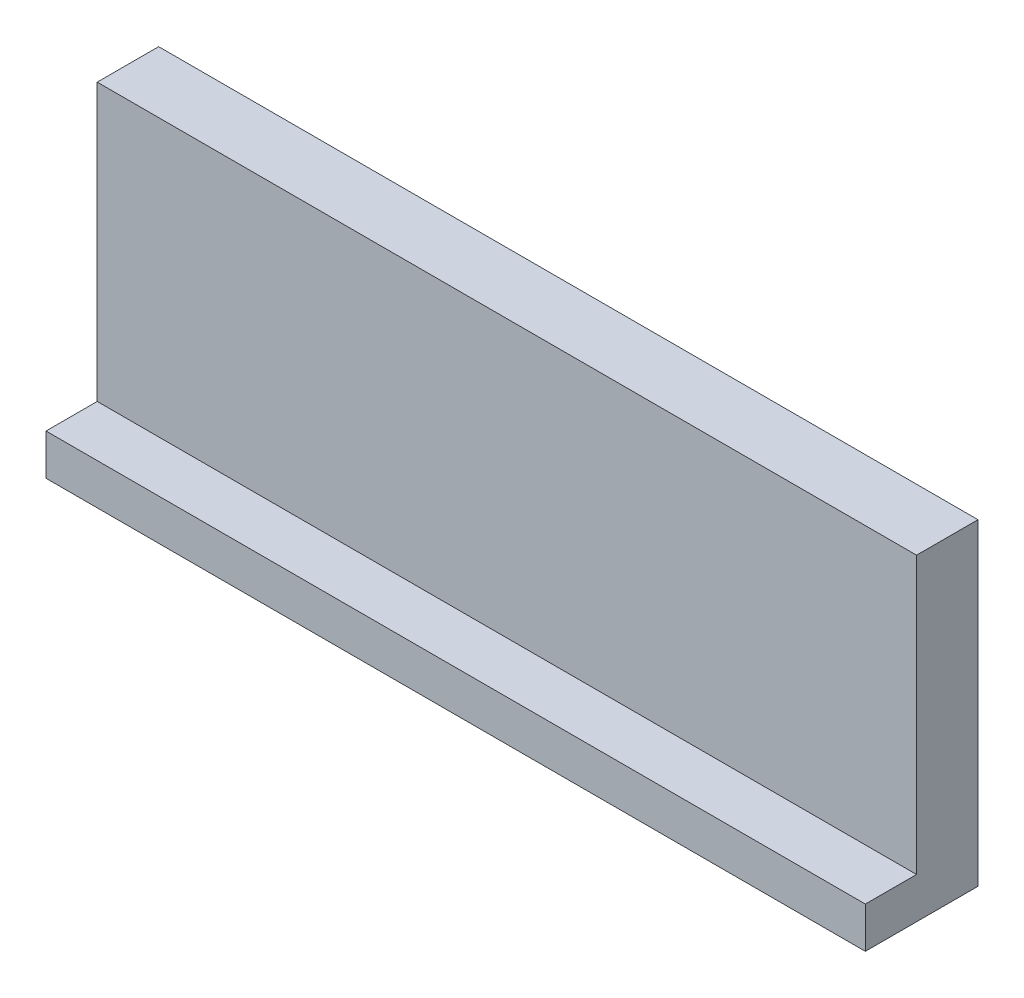
SolidWorks part; units mm, degrees
ref_plane "Alzado" through (0, 0, 0) normal (0, 0, 1) x (1, 0, 0)
ref_plane "Planta" through (0, 0, 0) normal (0, 1, 0) x (1, 0, 0)
ref_plane "Vista lateral" through (0, 0, 0) normal (1, 0, 0) x (0, 0, -1)
sketch "Croquis1" plane through (0, 0, 0) normal (0, 0, 1) x (1, 0, 0)
  line L1 (0, 0) -> (80, 0)
  line L2 (0, 0) -> (0, 31)
  line L3 (0, 31) -> (80, 31)
  line L4 (80, 0) -> (80, 31)
  dimension "D1" = 80
  dimension "D2" = 31
extrude "Saliente-Extruir1" add sketch "Croquis1" along normal blind 6
sketch "Croquis2" plane through (0, 0, 6) normal (0, 0, 1) x (1, 0, 0)
  line L0 (80, 0) -> (80, 31) construction
  line L1 (0, 0) -> (80, 0)
  line L2 (0, 0) -> (0, 4)
  line L3 (0, 4) -> (80, 4)
  line L4 (80, 0) -> (80, 4)
  dimension "D1" = 4
extrude "Saliente-Extruir2" add sketch "Croquis2" along normal blind 5
